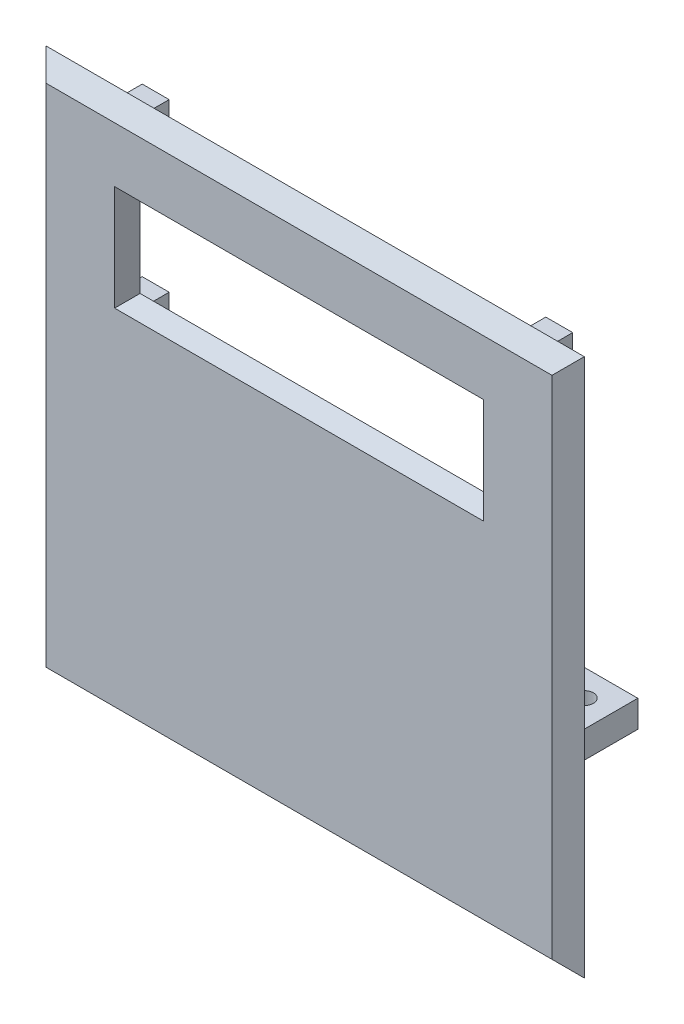
SolidWorks part; units mm, degrees
ref_plane "Plan de face" through (0, 0, 0) normal (0, 0, 1) x (1, 0, 0)
ref_plane "Plan de dessus" through (0, 0, 0) normal (0, 1, 0) x (1, 0, 0)
ref_plane "Plan de droite" through (0, 0, 0) normal (1, 0, 0) x (0, 0, -1)
sketch "Esquisse1" plane through (0, 0, 0) normal (0, 0, 1) x (1, 0, 0)
  line L1 (0, 0) -> (100, 0)
  line L2 (0, 0) -> (0, 100)
  line L3 (0, 100) -> (100, 100)
  line L4 (100, 0) -> (100, 100)
  dimension "D1" = 100
  dimension "D2" = 100
extrude "Boss.-Extru.1" add sketch "Esquisse1" along normal blind 3
sketch "Esquisse2" plane through (0, 0, 3) normal (0, 0, 1) x (1, 0, 0)
  line L0 (0, 100) -> (0, 0) construction
  line L1 (17.45, 85) -> (82.55, 85)
  line L2 (17.45, 85) -> (17.45, 68.9)
  line L3 (17.45, 68.9) -> (82.55, 68.9)
  line L4 (82.55, 85) -> (82.55, 68.9)
  line L5 (100, 100) -> (0, 100) construction
  dimension "D1" = 65.1
  dimension "D2" = 16.1
  dimension "D3" = 17.45
  dimension "D4" = 15
extrude "Enlèv. mat.-Extru.1" cut sketch "Esquisse2" against normal through all
chamfer "Chanfrein1" distance 3 angle 45 4 edges at (50, 0, 3) (0, 50, 3) (50, 100, 3) (100, 50, 3)
sketch "Esquisse3" plane through (0, 0, 0) normal (0, 0, -1) x (-1, 0, 0)
  line L0 (-82.55, 68.9) -> (-82.55, 85) construction
  line L1 (-90, 94.95) -> (-85, 94.95)
  line L2 (-90, 94.95) -> (-90, 89.95)
  line L3 (-90, 89.95) -> (-85, 89.95)
  line L4 (-85, 94.95) -> (-85, 89.95)
  line L5 (-15, 94.95) -> (-10, 94.95)
  line L6 (-15, 94.95) -> (-15, 89.95)
  line L7 (-15, 89.95) -> (-10, 89.95)
  line L8 (-10, 94.95) -> (-10, 89.95)
  line L9 (-90, 63.95) -> (-85, 63.95)
  line L10 (-90, 63.95) -> (-90, 58.95)
  line L11 (-90, 58.95) -> (-85, 58.95)
  line L12 (-85, 63.95) -> (-85, 58.95)
  line L13 (-15, 63.95) -> (-10, 63.95)
  line L14 (-15, 63.95) -> (-15, 58.95)
  line L15 (-15, 58.95) -> (-10, 58.95)
  line L16 (-10, 63.95) -> (-10, 58.95)
  line L17 (-17.45, 85) -> (-17.45, 68.9) construction
  line L18 (-82.55, 85) -> (-17.45, 85) construction
  line L19 (-17.45, 68.9) -> (-82.55, 68.9) construction
  circle A0 centre (-87.5, 92.45) radius 1.3
  circle A1 centre (-12.5, 92.45) radius 1.3
  circle A2 centre (-12.5, 61.45) radius 1.3
  circle A3 centre (-87.5, 61.45) radius 1.3
  dimension "D17" = 2.6
  dimension "D18" = 2.6
  dimension "D19" = 2.6
  dimension "D20" = 2.6
  dimension "D1" = 2.45
  dimension "D2" = 2.45
  dimension "D3" = 2.45
  dimension "D4" = 2.45
  dimension "D5" = 5
  dimension "D6" = 5
  dimension "D7" = 5
  dimension "D8" = 5
  dimension "D9" = 5
  dimension "D10" = 5
  dimension "D11" = 5
  dimension "D12" = 5
  dimension "D13" = 4.95
  dimension "D14" = 4.95
  dimension "D15" = 4.95
  dimension "D16" = 4.95
extrude "Boss.-Extru.2" add sketch "Esquisse3" along normal blind 7.85
chamfer "Chanfrein2" distance 3 angle 30 4 edges at (82.55, 76.95, 3) (50, 68.9, 3) (17.45, 76.95, 3) (50, 85, 3) first distance on face at (82.55, 76.95, 1.5) first distance on face at (50, 68.9, 1.5) first distance on face at (17.45, 76.95, 1.5) first distance on face at (50, 85, 1.5)
fillet "Congé1" radius 1 16 edges at (10, 61.45, 0) (12.5, 63.95, 0) (10, 92.45, 0) (12.5, 94.95, 0) (15, 92.45, 0) (12.5, 89.95, 0) (12.5, 58.95, 0) (15, 61.45, 0) (87.5, 94.95, 0) (90, 92.45, 0) (87.5, 63.95, 0) (85, 92.45, 0) (87.5, 89.95, 0) (85, 61.45, 0) (87.5, 58.95, 0) (90, 61.45, 0)
sketch "Esquisse4" plane through (0, 0, 0) normal (0, 0, -1) x (-1, 0, 0)
  line L0 (-100, 0) -> (-100, 100) construction
  line L1 (-99.95, 40) -> (-89.95, 40)
  line L2 (-99.95, 40) -> (-99.95, 35)
  line L3 (-99.95, 35) -> (-89.95, 35)
  line L4 (-89.95, 40) -> (-89.95, 35)
  line L5 (-10.05, 40) -> (-0.05, 40)
  line L6 (-10.05, 40) -> (-10.05, 35)
  line L7 (-10.05, 35) -> (-0.05, 35)
  line L8 (-0.05, 40) -> (-0.05, 35)
  line L9 (-100, 100) -> (0, 100) construction
  line L10 (0, 100) -> (0, 0) construction
  dimension "D1" = 0.05
  dimension "D2" = 10
  dimension "D3" = 5
  dimension "D4" = 60
  dimension "D5" = 60
  dimension "D6" = 0.05
  dimension "D7" = 10
  dimension "D8" = 5
extrude "Boss.-Extru.3" add sketch "Esquisse4" along normal blind 10
sketch "Esquisse5" plane through (0, 35, 0) normal (0, -1, 0) x (1, 0, 0)
  line L1 (0, 0) -> (100, 0) construction
  circle A0 centre (94.95, -5.05) radius 1.7
  circle A1 centre (5.05, -5.05) radius 1.7
  dimension "D1" = 3.4
  dimension "D2" = 3.4
  dimension "D3" = 5.05
  dimension "D4" = 5.05
extrude "Enlèv. mat.-Extru.2" cut sketch "Esquisse5" against normal blind 10
